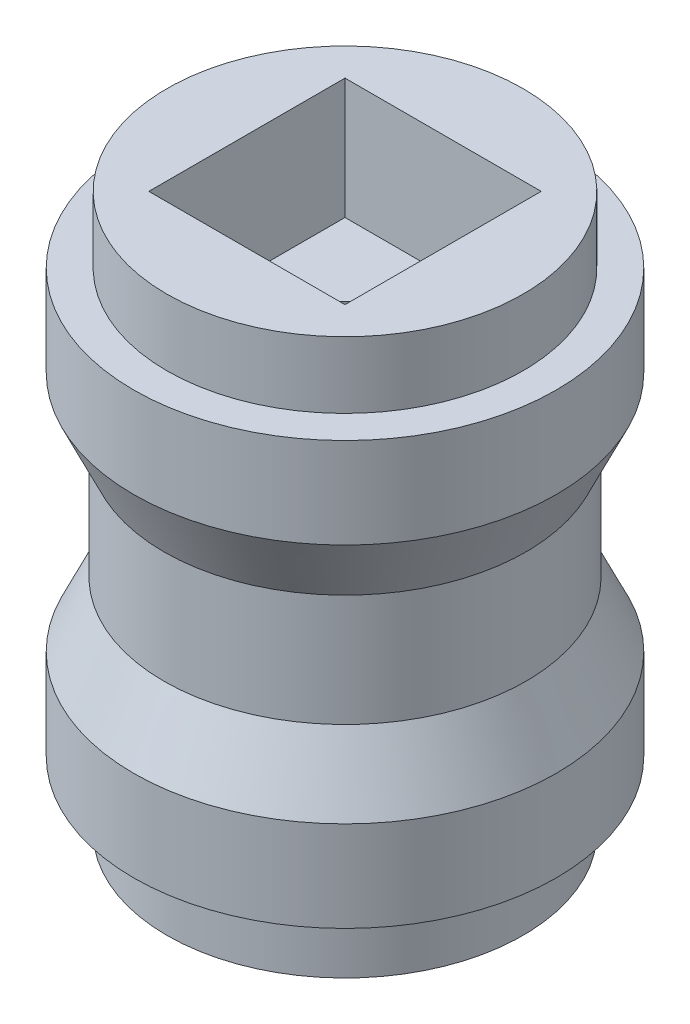
SolidWorks part; units mm, degrees
material "PET"
ref_plane "Спереди" through (0, 0, 0) normal (0, 0, 1) x (1, 0, 0)
ref_plane "Сверху" through (0, 0, 0) normal (0, 1, 0) x (1, 0, 0)
ref_plane "Справа" through (0, 0, 0) normal (1, 0, 0) x (0, 0, -1)
sketch "Эскиз1" plane through (0, 0, 0) normal (0, 1, 0) x (1, 0, 0)
  circle A0 centre (0, 0) radius 7
  dimension "D1" = 14
extrude "Бобышка-Вытянуть1" add sketch "Эскиз1" along normal blind 3
sketch "Эскиз2" plane through (0, 3, 0) normal (0, 1, 0) x (1, 0, 0)
  circle A0 centre (0, 0) radius 6
  dimension "D1" = 12
extrude "Бобышка-Вытянуть2" add sketch "Эскиз2" along normal blind 8
sketch "Эскиз3" plane through (0, 11, 0) normal (0, 1, 0) x (1, 0, 0)
  circle A0 centre (0, 0) radius 7
extrude "Бобышка-Вытянуть3" add sketch "Эскиз3" along normal blind 3
chamfer "Фаска1" distance 1 angle 65 1 edges at (0, 3, 6) first distance on face at (0, 3, 6)
chamfer "Фаска2" distance 1 angle 65 1 edges at (0, 11, 6) first distance on face at (0, 11, 6)
sketch "Эскиз4" plane through (0, 14, 0) normal (0, 1, 0) x (1, 0, 0)
  circle A0 centre (0, 0) radius 5.9
  dimension "D1" = 11.8
extrude "Бобышка-Вытянуть4" add sketch "Эскиз4" along normal blind 2.2
sketch "Эскиз5" plane through (0, 0, 0) normal (0, -1, 0) x (1, 0, 0)
  circle A0 centre (0, 0) radius 5.9
  dimension "D1" = 11.8
extrude "Бобышка-Вытянуть5" add sketch "Эскиз5" along normal blind 2.2
sketch "Эскиз6" plane through (0, 16.2, 0) normal (0, 1, 0) x (1, 0, 0)
  line L1 (-3.25, 3.25) -> (3.25, 3.25)
  line L2 (-3.25, 3.25) -> (-3.25, -3.25)
  line L3 (-3.25, -3.25) -> (3.25, -3.25)
  line L4 (3.25, 3.25) -> (3.25, -3.25)
  line L5 (-3.25, 3.25) -> (3.25, -3.25) construction
  line L6 (-3.25, -3.25) -> (3.25, 3.25) construction
  point P0 (0, 0)
  dimension "D1" = 6.5
  dimension "D2" = 6.5
extrude "Вырез-Вытянуть1" cut sketch "Эскиз6" against normal blind 4
sketch "Эскиз7" plane through (0, -2.2, 0) normal (0, -1, 0) x (1, 0, 0)
  line L1 (-3.25, 3.25) -> (3.25, 3.25)
  line L2 (-3.25, 3.25) -> (-3.25, -3.25)
  line L3 (-3.25, -3.25) -> (3.25, -3.25)
  line L4 (3.25, 3.25) -> (3.25, -3.25)
  line L5 (-3.25, 3.25) -> (3.25, -3.25) construction
  line L6 (-3.25, -3.25) -> (3.25, 3.25) construction
  point P0 (0, 0)
  dimension "D1" = 6.5
  dimension "D2" = 6.5
extrude "Вырез-Вытянуть2" cut sketch "Эскиз7" against normal blind 4
sketch "Эскиз8" plane through (0, 1.8, 0) normal (0, -1, 0) x (1, 0, 0)
  circle A0 centre (0, 0) radius 1.2
  dimension "D1" = 2.4
extrude "Вырез-Вытянуть3" cut sketch "Эскиз8" against normal through all
